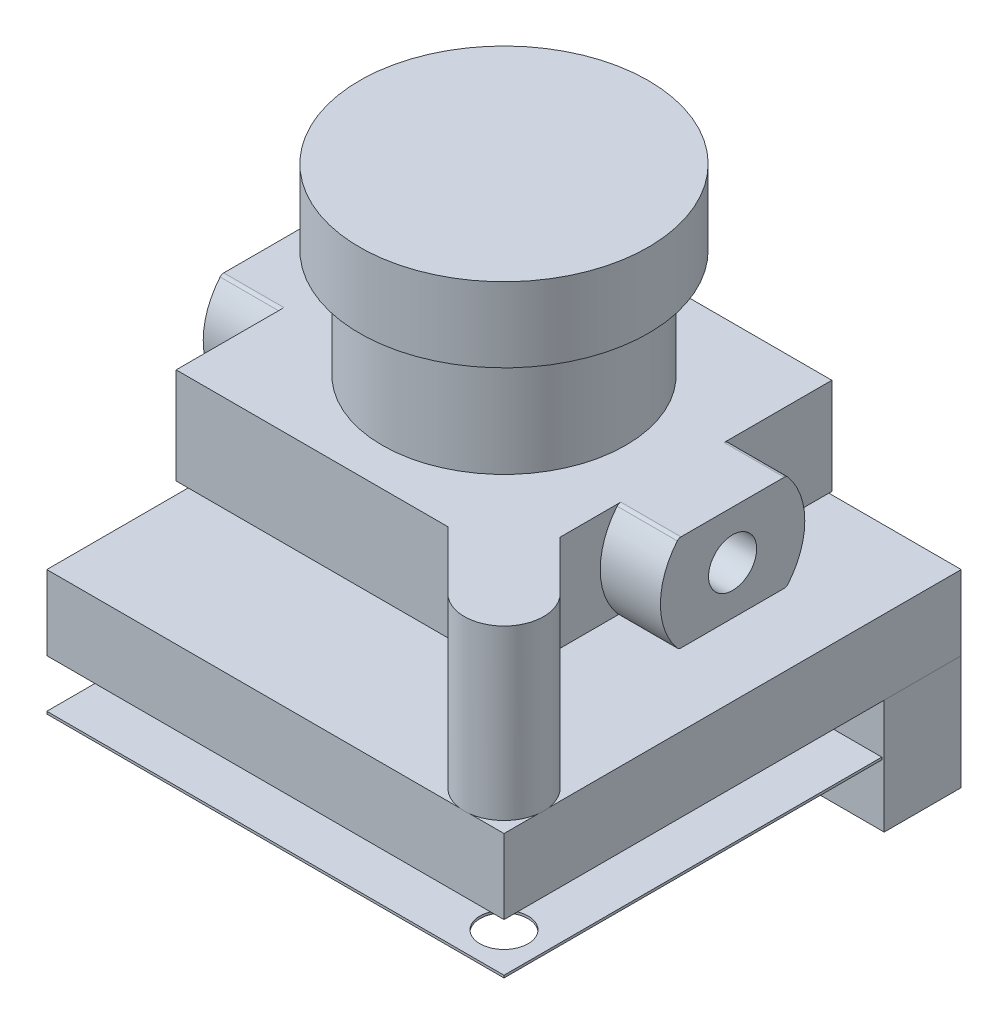
SolidWorks part; units mm, degrees
ref_plane "Front Plane" through (0, 0, 0) normal (0, 0, 1) x (1, 0, 0)
ref_plane "Top Plane" through (0, 0, 0) normal (0, 1, 0) x (1, 0, 0)
ref_plane "Right Plane" through (0, 0, 0) normal (1, 0, 0) x (0, 0, -1)
sketch "MainBoard" plane through (0, 0, 0) normal (0, 1, 0) x (1, 0, 0)
  line L0 (0.1, 6.7) -> (3.5, 6.7)
  line L1 (-9.5, -9.5) -> (9.5, -9.5)
  line L2 (-9.5, -9.5) -> (-9.5, 9.5)
  line L3 (-9.5, 9.5) -> (9.5, 9.5)
  line L4 (9.5, -9.5) -> (9.5, 9.5)
  line L5 (-9.5, -9.5) -> (9.5, 9.5) construction
  line L6 (-9.5, 9.5) -> (9.5, -9.5) construction
  line L7 (4, 9.5) -> (9.5, 9.5)
  line L8 (4, 9.5) -> (4, 6.3)
  line L9 (4, 6.3) -> (9.5, 6.3)
  line L10 (9.5, 9.5) -> (9.5, 6.3)
  line L11 (-0.3, 9.5) -> (3.9, 9.5)
  line L12 (-0.3, 9.5) -> (-0.3, 6.3)
  line L13 (-0.3, 6.3) -> (3.9, 6.3)
  line L14 (3.9, 9.5) -> (3.9, 6.3)
  line L15 (3.5, 9.1) -> (3.5, 6.7)
  line L16 (0.1, 9.1) -> (3.5, 9.1)
  line L17 (0.1, 9.1) -> (0.1, 6.7)
  line L18 (4.4, 9.1) -> (9.1, 9.1)
  line L19 (4.4, 9.1) -> (4.4, 6.7)
  line L20 (4.4, 6.7) -> (9.1, 6.7)
  line L21 (9.1, 9.1) -> (9.1, 6.7)
  circle A0 centre (-7.8666, 7.8666) radius 1
  circle A1 centre (7.8666, -7.8666) radius 1
  point P0 (0, 0)
  point P25 (7.8162, -7.8162)
  dimension "D8" = 2
  dimension "D1" = 19
  dimension "D2" = 5.5
  dimension "D3" = 3.2
  dimension "D4" = 4.2
  dimension "D5" = 0.1
  dimension "D7" = 22.25
  dimension "D6" = 0.4
sketch "LensBody_Main" plane through (0, 0, 0) normal (0, 1, 0) x (1, 0, 0)
  line L0 (-9.0333, 6.6998) -> (-7, 4.6665)
  line L1 (-7, -6.625) -> (4.2915, -6.625)
  line L2 (-7, -6.625) -> (-7, 4.6665)
  line L3 (0, -6.625) -> (0, 6.625) construction
  line L4 (-9.5, 9.5) -> (9.5, -9.5) construction
  line L6 (7, 0) -> (-7, 0) construction
  line L13 (-6.6998, 9.0333) -> (-4.2915, 6.625)
  line L16 (-4.2915, 6.625) -> (7, 6.625)
  line L17 (7, -4.6665) -> (7, 6.625)
  line L21 (7, -4.6665) -> (9.0333, -6.6998)
  line L22 (4.2915, -6.625) -> (6.6998, -9.0333)
  arc A2 (-6.6998, 9.0333) -> (-9.0333, 6.6998) centre (-7.8666, 7.8666) ccw
  arc A3 (6.6998, -9.0333) -> (9.0333, -6.6998) centre (7.8666, -7.8666) ccw
  point P2 (0, 0)
  point P5 (-7.4969, 7.4969)
  point P6 (0, 0)
  point P9 (0, 0)
  point P12 (0, 0)
  point P14 (0, 0)
  point P15 (0, 0)
  point P28 (0, 0)
  point P30 (0, 0)
  dimension "D1" = 1.65
  dimension "D2" = 13.25
  dimension "D3" = 14
sketch "LensBody_Sub" plane through (0, 0, 0) normal (0, 1, 0) x (1, 0, 0)
  circle A0 centre (-7.8666, 7.8666) radius 1.65
  circle A1 centre (7.8666, -7.8666) radius 1.65
extrude "Boss-LensBodySub" add sketch "LensBody_Sub" along normal blind 3
extrude "Boss-LensBodyMain" add sketch "LensBody_Main" along normal blind 4 from offset 3 contours L2 L0 A2 L13 L16 L17 L21 A3 L22 L1
sketch "Sketch4" plane through (0, 7, 0) normal (0, 1, 0) x (1, 0, 0)
  circle A0 centre (0, 0) radius 5.06
  dimension "D1" = 10.12
extrude "Boss-LensBodyShaft" add sketch "Sketch4" along normal blind 4.5
sketch "Sketch7" plane through (0, 0, 0) normal (1, 0, 0) x (0, 0, -1)
  line L0 (4.6665, 7) -> (4.6665, 3) construction
  line L1 (2.1448, 3) -> (-2.1448, 3)
  line L2 (-6.625, 3) -> (4.6665, 3) construction
  line L3 (-2.1448, 7) -> (2.1448, 7)
  line L4 (5.06, 7) -> (-5.06, 7) construction
  arc A0 (2.298, 3.0714) -> (2.298, 6.9286) centre (0, 5) ccw
  arc A1 (-2.298, 6.9286) -> (-2.298, 3.0714) centre (0, 5) ccw
  arc A2 (-2.1448, 3) -> (-2.298, 3.0714) centre (-2.1448, 3.2) cw
  arc A3 (-2.1448, 7) -> (-2.298, 6.9286) centre (-2.1448, 6.8) ccw
  arc A4 (2.1448, 7) -> (2.298, 6.9286) centre (2.1448, 6.8) cw
  arc A5 (2.1448, 3) -> (2.298, 3.0714) centre (2.1448, 3.2) ccw
  circle A6 centre (0, 5) radius 1
  point P6 (4.6665, 5)
  point P18 (-2.2361, 7)
  dimension "D1" = 6
  dimension "D2" = 0.2
  dimension "D3" = 2
extrude "Boss-Extrude8" add sketch "Sketch7" along normal mid plane 19
sketch "Sketch5" plane through (0, 11.5, 0) normal (0, 1, 0) x (1, 0, 0)
  circle A0 centre (0, 0) radius 6
  dimension "D1" = 12
extrude "Boss-Lens" add sketch "Sketch5" along normal blind 3.1 separate body
extrude "Boss-MainBoard" add sketch "MainBoard" against normal blind 3.1 separate body contours L3 L2 L1 L4
extrude "Boss-Jacks" add sketch "MainBoard<4>" against normal blind 4.75 from surface separate body contours L14 L3 L12 L13 L17 L16 L15 L0 | L8 L9 L4 L3 L18 L21 L20 L19 region at (6.75, 0, -6.3636) region at (1.8, 0, -9.4472) starting at face at (0, -3.1, 0)
sketch "MainBoard<4>" plane through (0, 0, 0) normal (0, 1, 0) x (1, 0, 0) same geometry as "MainBoard"
sketch "Sketch6" plane through (0, -3.1, 0) normal (0, -1, 0) x (1, 0, 0)
  line L0 (-9.5, -9.5) -> (-0.4, -9.5)
  line L1 (-9.5, -9.5) -> (9.5, -9.5) construction
  line L2 (-0.4, -9.5) -> (-0.4, -6.2)
  line L3 (-0.4, -6.2) -> (9.5, -6.2)
  line L4 (9.5, -6.2) -> (9.5, 9.5)
  line L5 (9.5, 9.5) -> (-9.5, 9.5)
  line L6 (-9.5, 9.5) -> (-9.5, -9.5)
  line L7 (3.9, -6.3) -> (-0.3, -6.3) construction
  line L8 (-0.3, -6.3) -> (-0.3, -9.5) construction
  dimension "D1" = 0.1
  dimension "D2" = 0.1
extrude "Boss-BackClearance" add sketch "Sketch6" along normal blind 0.1 from offset 2 separate body
extrude "Cut-Screws" cut sketch "MainBoard<3>" along normal blind 5 and the other way through all contours A1 | A0
sketch "MainBoard<3>" plane through (0, 0, 0) normal (0, 1, 0) x (1, 0, 0) same geometry as "MainBoard"
